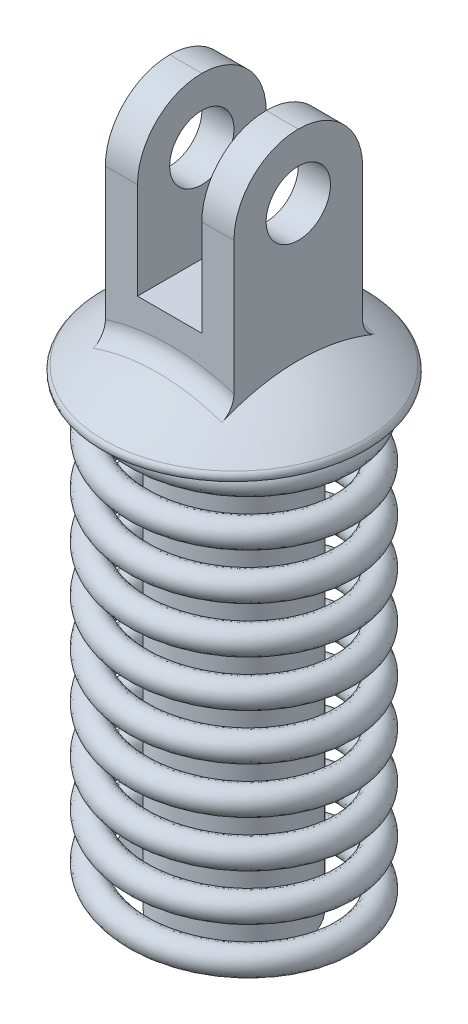
SolidWorks part; units mm, degrees
ref_plane "Front Plane" through (0, 0, 0) normal (0, 0, 1) x (1, 0, 0)
ref_plane "Top Plane" through (0, 0, 0) normal (0, 1, 0) x (1, 0, 0)
ref_plane "Right Plane" through (0, 0, 0) normal (1, 0, 0) x (0, 0, -1)
sketch "Sketch2" plane through (0, 0, 0) normal (1, 0, 0) x (0, 0, -1)
  line L0 (0, 8.2798) -> (0, -18.2424) construction
  line L2 (0, 3.646) -> (0, 1.5374)
  line L4 (-5.12, 1.5374) -> (0, 1.5374)
  arc A0 (0, 3.646) -> (-5.0559, 1.8459) centre (0, -4.354) ccw
  arc A1 (-5.12, 1.5374) -> (-5.0559, 1.8459) centre (-4.8979, 1.6521) cw
  dimension "D2" = 0.25
  dimension "D3" = 16
revolve "Revolve1" add sketch "Sketch2" angle 360 about L0
sketch "Sketch3" plane through (0, 1.5374, 0) normal (0, -1, 0) x (1, 0, 0)
  circle A0 centre (0, 0) radius 2.5
  dimension "D1" = 5
extrude "Boss-Extrude1" add sketch "Sketch3" along normal blind 18
sketch "Sketch4" plane through (0, 1.5374, 0) normal (0, -1, 0) x (1, 0, 0)
  circle A0 centre (0, 0) radius 4
  dimension "D1" = 8
curve "Helix/Spiral1" pitch 1.8 height 18 radius 4 left hand yes centre (0, 1.5374, 0) axis (0, -1, 0) start towards (0, 0, -1)
sketch "Sketch6" plane through (0, 0, 0) normal (0, 0, 1) x (1, 0, 0)
  line L0 (-5.12, 1.5374) -> (5.12, 1.5374) construction
  circle A0 centre (-4, 1.5374) radius 0.5
  spline S0 degree 3 poles (-4, 1.5374) (-4, 1.5002) (-3.7917, 1.4248) (-2.9021, 1.3125) (-1.5706, 1.1999) (0, 1.0874) (1.5706, 0.9749) (2.9021, 0.8624) (3.7917, 0.7499) (4.1041, 0.6374) (3.7917, 0.5249) (2.9021, 0.4124) (1.5706, 0.2999) (0, 0.1874) (-1.5706, 0.0749) (-2.9021, -0.0376) (-3.7917, -0.1501) (-4.1041, -0.2626) (-3.7917, -0.3751) (-2.9021, -0.4876) (-1.5706, -0.6001) (0, -0.7126) (1.5706, -0.8251) (2.9021, -0.9376) (3.7917, -1.0501) (4.1041, -1.1626) (3.7917, -1.2751) (2.9021, -1.3876) (1.5706, -1.5001) (0, -1.6126) (-1.5706, -1.7251) (-2.9021, -1.8376) (-3.7917, -1.9501) (-4.1041, -2.0626) (-3.7917, -2.1751) (-2.9021, -2.2876) (-1.5706, -2.4001) (0, -2.5126) (1.5706, -2.6251) (2.9021, -2.7376) (3.7917, -2.8501) (4.1041, -2.9626) (3.7917, -3.0751) (2.9021, -3.1876) (1.5706, -3.3001) (0, -3.4126) (-1.5706, -3.5251) (-2.9021, -3.6376) (-3.7917, -3.7501) (-4.1041, -3.8626) (-3.7917, -3.9751) (-2.9021, -4.0876) (-1.5706, -4.2001) (0, -4.3126) (1.5706, -4.4251) (2.9021, -4.5376) (3.7917, -4.6501) (4.1041, -4.7626) (3.7917, -4.8751) (2.9021, -4.9876) (1.5706, -5.1001) (0, -5.2126) (-1.5706, -5.3251) (-2.9021, -5.4376) (-3.7917, -5.5501) (-4.1041, -5.6626) (-3.7917, -5.7751) (-2.9021, -5.8876) (-1.5706, -6.0001) (0, -6.1126) (1.5706, -6.2251) (2.9021, -6.3376) (3.7917, -6.4501) (4.1041, -6.5626) (3.7917, -6.6751) (2.9021, -6.7876) (1.5706, -6.9001) (0, -7.0126) (-1.5706, -7.1251) (-2.9021, -7.2376) (-3.7917, -7.3501) (-4.1041, -7.4626) (-3.7917, -7.5751) (-2.9021, -7.6876) (-1.5706, -7.8001) (0, -7.9126) (1.5706, -8.0251) (2.9021, -8.1376) (3.7917, -8.2501) (4.1041, -8.3626) (3.7917, -8.4751) (2.9021, -8.5876) (1.5706, -8.7001) (0, -8.8126) (-1.5706, -8.9251) (-2.9021, -9.0376) (-3.7917, -9.1501) (-4.1041, -9.2626) (-3.7917, -9.3751) (-2.9021, -9.4876) (-1.5706, -9.6001) (0, -9.7126) (1.5706, -9.8251) (2.9021, -9.9376) (3.7917, -10.0501) (4.1041, -10.1626) (3.7917, -10.2751) (2.9021, -10.3876) (1.5706, -10.5001) (0, -10.6126) (-1.5706, -10.7251) (-2.9021, -10.8376) (-3.7917, -10.9501) (-4.1041, -11.0626) (-3.7917, -11.1751) (-2.9021, -11.2876) (-1.5706, -11.4001) (0, -11.5126) (1.5706, -11.6251) (2.9021, -11.7376) (3.7917, -11.8501) (4.1041, -11.9626) (3.7917, -12.0751) (2.9021, -12.1876) (1.5706, -12.3001) (0, -12.4126) (-1.5706, -12.5251) (-2.9021, -12.6376) (-3.7917, -12.7501) (-4.1041, -12.8626) (-3.7917, -12.9751) (-2.9021, -13.0876) (-1.5706, -13.2001) (0, -13.3126) (1.5706, -13.4251) (2.9021, -13.5376) (3.7917, -13.6501) (4.1041, -13.7626) (3.7917, -13.8751) (2.9021, -13.9876) (1.5706, -14.1001) (0, -14.2126) (-1.5706, -14.3251) (-2.9021, -14.4376) (-3.7917, -14.5501) (-4.1041, -14.6626) (-3.7917, -14.7751) (-2.9021, -14.8876) (-1.5706, -15.0001) (0, -15.1126) (1.5706, -15.2251) (2.9021, -15.3376) (3.7917, -15.4501) (4.1041, -15.5626) (3.7917, -15.6751) (2.9021, -15.7876) (1.5706, -15.9001) (0, -16.0126) (-1.5706, -16.1251) (-2.9021, -16.2376) (-3.7917, -16.35) (-4, -16.4253) (-4, -16.4626) knots 0 0 0 0 0.00625 0.0125 0.01875 0.025 0.03125 0.0375 0.04375 0.05 0.05625 0.0625 0.06875 0.075 0.08125 0.0875 0.09375 0.1 0.10625 0.1125 0.11875 0.125 0.13125 0.1375 0.14375 0.15 0.15625 0.1625 0.16875 0.175 0.18125 0.1875 0.19375 0.2 0.20625 0.2125 0.21875 0.225 0.23125 0.2375 0.24375 0.25 0.25625 0.2625 0.26875 0.275 0.28125 0.2875 0.29375 0.3 0.30625 0.3125 0.31875 0.325 0.33125 0.3375 0.34375 0.35 0.35625 0.3625 0.36875 0.375 0.38125 0.3875 0.39375 0.4 0.40625 0.4125 0.41875 0.425 0.43125 0.4375 0.44375 0.45 0.45625 0.4625 0.46875 0.475 0.48125 0.4875 0.49375 0.5 0.50625 0.5125 0.51875 0.525 0.53125 0.5375 0.54375 0.55 0.55625 0.5625 0.56875 0.575 0.58125 0.5875 0.59375 0.6 0.60625 0.6125 0.61875 0.625 0.63125 0.6375 0.64375 0.65 0.65625 0.6625 0.66875 0.675 0.68125 0.6875 0.69375 0.7 0.70625 0.7125 0.71875 0.725 0.73125 0.7375 0.74375 0.75 0.75625 0.7625 0.76875 0.775 0.78125 0.7875 0.79375 0.8 0.80625 0.8125 0.81875 0.825 0.83125 0.8375 0.84375 0.85 0.85625 0.8625 0.86875 0.875 0.88125 0.8875 0.89375 0.9 0.90625 0.9125 0.91875 0.925 0.93125 0.9375 0.94375 0.95 0.95625 0.9625 0.96875 0.975 0.98125 0.9875 0.99375 1 1 1 1 construction
  dimension "D1" = 1
sweep "Sweep1" add profiles "Sketch6" path "Helix/Spiral1"
ref_plane "Plane1" through (0, 15, 0) normal (0, 1, 0) x (1, 0, 0)
sketch "Sketch7" plane through (0, 15, 0) normal (0, 1, 0) x (1, 0, 0)
  line L1 (2.5, 2.5) -> (-2.5, 2.5)
  line L2 (2.5, 2.5) -> (2.5, -2.5)
  line L3 (2.5, -2.5) -> (-2.5, -2.5)
  line L4 (-2.5, 2.5) -> (-2.5, -2.5)
  line L5 (2.5, 2.5) -> (-2.5, -2.5) construction
  line L6 (2.5, -2.5) -> (-2.5, 2.5) construction
  point P0 (0, 0)
  dimension "D1" = 5
  dimension "D2" = 5
extrude "Boss-Extrude2" add sketch "Sketch7" against normal up to surface (12.1777 mm away) up to face at (0, 1.8459, 5.0559)
sketch "Sketch8" plane through (0, 0, 2.5) normal (0, 0, 1) x (1, 0, 0)
  line L0 (-2.5, 8.5374) -> (2.5, 8.5374)
  line L1 (-2.5, 2.8223) -> (-2.5, 15) construction
  line L2 (2.5, 2.8223) -> (2.5, 15) construction
  line L3 (-2.5, -16.4626) -> (2.5, -16.4626) construction
  line L4 (-1.25, 15) -> (-1.25, 4.7874)
  line L5 (-2.5, 15) -> (2.5, 15) construction
  line L6 (-1.25, 4.7874) -> (1.25, 4.7874)
  line L7 (1.25, 4.7874) -> (1.25, 15)
  line L8 (1.25, 15) -> (2.5, 15)
  line L9 (-1.25, 15) -> (1.25, 15)
  line L10 (-2.5, 11.0374) -> (2.5, 11.0374)
  line M5 (2.5, 2.8223) -> (2.5, 15)
  line M6 (2.5, 15) -> (-2.5, 15)
  line M7 (-2.5, 15) -> (-2.5, 2.8223)
  dimension "D1" = 25
  dimension "D2" = 1.25
  dimension "D3" = 1.25
  dimension "D4" = 6.25
  dimension "D5" = 2.5
extrude "Cut-Extrude2" cut sketch "Sketch8" against normal blind 18 contours L10 L4 M7 M6 | L4 L10 L7 M6 | L7 L10 M5 M6 | L10 L4 L0 L7 | L6 L7 L0 L4
fillet "Fillet1" radius 2.5 4 edges at (-1.875, 11.0374, 2.5) (-1.875, 11.0374, -2.5) (1.875, 11.0374, -2.5) (1.875, 11.0374, 2.5)
sketch "Sketch9" plane through (-2.5, 0, 0) normal (-1, 0, 0) x (0, 0, 1)
  circle A0 centre (0, 8.5374) radius 1.25
  dimension "D1" = 2.5
extrude "Cut-Extrude3" cut sketch "Sketch9" against normal blind 18
fillet "Fillet2" radius 0.75 2 edges at (0, 3.2453, -2.5) (0, 3.2453, 2.5)
